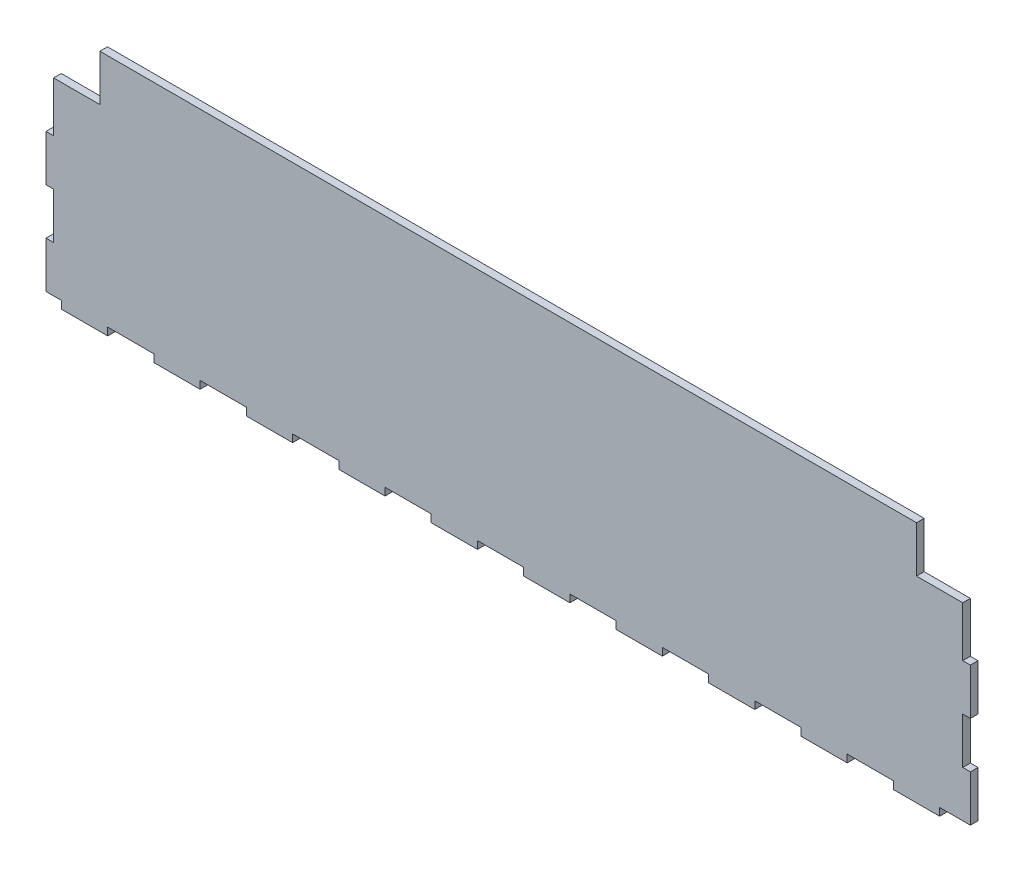
SolidWorks part; units mm, degrees
material "Balsa"
ref_plane "Front Plane" through (0, 0, 0) normal (0, 0, 1) x (1, 0, 0)
ref_plane "Top Plane" through (0, 0, 0) normal (0, 1, 0) x (1, 0, 0)
ref_plane "Right Plane" through (0, 0, 0) normal (1, 0, 0) x (0, 0, -1)
sketch "Sketch1" plane through (0, 0, 0) normal (0, 0, 1) x (1, 0, 0)
  line L0 (393.4, -121.5124) -> (393.4, -39.8043)
  line L1 (393.4, -39.8043) -> (0, -39.8043) construction
  line L2 (0, -39.8043) -> (0, -121.5124)
  line L3 (0, -121.5124) -> (393.4, -121.5124)
  line L4 (0, -138.3774) -> (0, -39.8043) construction
  line L5 (373.4, -39.8043) -> (20, -39.8043) construction
  line L6 (373.4, -39.8043) -> (373.4, -19.8043)
  line L7 (373.4, -19.8043) -> (20, -19.8043)
  line L8 (20, -39.8043) -> (20, -19.8043)
  line L9 (373.4, -39.8043) -> (20, -19.8043) construction
  line L10 (373.4, -19.8043) -> (20, -39.8043) construction
  line L13 (20.7, -19.8043) -> (372.7, -19.8043) construction
  line L14 (393.4, -39.8043) -> (393.4, -138.3812) construction
  line L19 (393.4, -39.8043) -> (373.4, -39.8043)
  line L20 (0, -39.8043) -> (20, -39.8043)
  point P12 (196.7, -29.8043)
  dimension "D1" = 20
  dimension "D2" = 20
  dimension "D3" = 20
extrude "Boss-Extrude1" add sketch "Sketch1" against normal blind 3.3 contours L2 L3 L0 L1 | L8 L1 L6 L7 region at (196.7, -71.4918, 0)
sketch "Sketch2" plane through (0, 0, 0) normal (0, 0, 1) x (1, 0, 0)
  line L0 (343.4, -121.5124) -> (323.4, -121.5124)
  line L1 (383.4, -121.5124) -> (363.4, -121.5124)
  line L2 (383.4, -121.5124) -> (383.4, -124.8124)
  line L3 (383.4, -124.8124) -> (363.4, -124.8124)
  line L4 (363.4, -121.5124) -> (363.4, -124.8124)
  line L5 (383.4, -121.5124) -> (363.4, -124.8124) construction
  line L6 (383.4, -124.8124) -> (363.4, -121.5124) construction
  line L7 (343.4, -121.5124) -> (343.4, -124.8124)
  line L8 (343.4, -124.8124) -> (323.4, -124.8124)
  line L9 (323.4, -121.5124) -> (323.4, -124.8124)
  line L10 (343.4, -121.5124) -> (323.4, -124.8124) construction
  line L11 (343.4, -124.8124) -> (323.4, -121.5124) construction
  line L12 (303.4, -121.5124) -> (283.4, -121.5124)
  line L13 (303.4, -121.5124) -> (303.4, -124.8124)
  line L14 (303.4, -124.8124) -> (283.4, -124.8124)
  line L15 (283.4, -121.5124) -> (283.4, -124.8124)
  line L16 (303.4, -121.5124) -> (283.4, -124.8124) construction
  line L17 (303.4, -124.8124) -> (283.4, -121.5124) construction
  line L18 (263.4, -121.5124) -> (243.4, -121.5124)
  line L19 (263.4, -121.5124) -> (263.4, -124.8124)
  line L20 (263.4, -124.8124) -> (243.4, -124.8124)
  line L21 (243.4, -121.5124) -> (243.4, -124.8124)
  line L22 (263.4, -121.5124) -> (243.4, -124.8124) construction
  line L23 (263.4, -124.8124) -> (243.4, -121.5124) construction
  line L24 (223.4, -121.5124) -> (203.4, -121.5124)
  line L25 (223.4, -121.5124) -> (223.4, -124.8124)
  line L26 (223.4, -124.8124) -> (203.4, -124.8124)
  line L27 (203.4, -121.5124) -> (203.4, -124.8124)
  line L28 (223.4, -121.5124) -> (203.4, -124.8124) construction
  line L29 (223.4, -124.8124) -> (203.4, -121.5124) construction
  line L30 (183.4, -121.5124) -> (163.4, -121.5124)
  line L31 (183.4, -121.5124) -> (183.4, -124.8124)
  line L32 (183.4, -124.8124) -> (163.4, -124.8124)
  line L33 (163.4, -121.5124) -> (163.4, -124.8124)
  line L34 (183.4, -121.5124) -> (163.4, -124.8124) construction
  line L35 (183.4, -124.8124) -> (163.4, -121.5124) construction
  line L36 (143.4, -121.5124) -> (123.4, -121.5124)
  line L37 (143.4, -121.5124) -> (143.4, -124.8124)
  line L38 (143.4, -124.8124) -> (123.4, -124.8124)
  line L39 (123.4, -121.5124) -> (123.4, -124.8124)
  line L40 (143.4, -121.5124) -> (123.4, -124.8124) construction
  line L41 (143.4, -124.8124) -> (123.4, -121.5124) construction
  line L42 (103.4, -121.5124) -> (83.4, -121.5124)
  line L43 (103.4, -121.5124) -> (103.4, -124.8124)
  line L44 (103.4, -124.8124) -> (83.4, -124.8124)
  line L45 (83.4, -121.5124) -> (83.4, -124.8124)
  line L46 (103.4, -121.5124) -> (83.4, -124.8124) construction
  line L47 (103.4, -124.8124) -> (83.4, -121.5124) construction
  line L48 (63.4, -121.5124) -> (43.4, -121.5124)
  line L49 (63.4, -121.5124) -> (63.4, -124.8124)
  line L50 (63.4, -124.8124) -> (43.4, -124.8124)
  line L51 (43.4, -121.5124) -> (43.4, -124.8124)
  line L52 (63.4, -121.5124) -> (43.4, -124.8124) construction
  line L53 (63.4, -124.8124) -> (43.4, -121.5124) construction
  line L54 (23.4, -121.5124) -> (3.4, -121.5124)
  line L55 (23.4, -121.5124) -> (23.4, -124.8124)
  line L56 (23.4, -124.8124) -> (3.4, -124.8124)
  line L57 (3.4, -121.5124) -> (3.4, -124.8124)
  line L58 (23.4, -121.5124) -> (3.4, -124.8124) construction
  line L59 (23.4, -124.8124) -> (3.4, -121.5124) construction
  point P4 (373.4, -123.1624)
  point P13 (333.4, -123.1624)
  point P18 (293.4, -123.1624)
  point P23 (253.4, -123.1624)
  point P28 (213.4, -123.1624)
  point P33 (173.4, -123.1624)
  point P38 (133.4, -123.1624)
  point P43 (93.4, -123.1624)
  point P48 (53.4, -123.1624)
  point P53 (13.4, -123.1624)
  dimension "D1" = 10
extrude "Boss-Extrude2" add sketch "Sketch2" against normal blind 3.3
sketch "Sketch3" plane through (0, 0, 0) normal (0, 0, 1) x (1, 0, 0)
  line L0 (396.7, -39.8043) -> (396.7, -61.5124) construction
  line L1 (393.4, -121.5124) -> (396.7, -121.5124)
  line L2 (393.4, -121.5124) -> (393.4, -101.5124)
  line L3 (393.4, -101.5124) -> (396.7, -101.5124)
  line L4 (396.7, -121.5124) -> (396.7, -101.5124)
  line L5 (393.4, -121.5124) -> (396.7, -101.5124) construction
  line L6 (393.4, -101.5124) -> (396.7, -121.5124) construction
  line L7 (393.4, -81.5124) -> (396.7, -81.5124)
  line L8 (393.4, -81.5124) -> (393.4, -61.5124)
  line L9 (393.4, -61.5124) -> (396.7, -61.5124)
  line L10 (396.7, -81.5124) -> (396.7, -61.5124)
  line L11 (393.4, -81.5124) -> (396.7, -61.5124) construction
  line L12 (393.4, -61.5124) -> (396.7, -81.5124) construction
  line L15 (-3.3, -124.4404) -> (-3.3, -121.5124) construction
  line L16 (0, -121.5124) -> (-3.3, -121.5124)
  line L17 (0, -121.5124) -> (0, -101.5124)
  line L18 (0, -101.5124) -> (-3.3, -101.5124)
  line L19 (-3.3, -121.5124) -> (-3.3, -101.5124)
  line L20 (0, -121.5124) -> (-3.3, -101.5124) construction
  line L21 (0, -101.5124) -> (-3.3, -121.5124) construction
  line L22 (0, -81.5124) -> (-3.3, -81.5124)
  line L23 (0, -81.5124) -> (0, -61.5124)
  line L24 (0, -61.5124) -> (-3.3, -61.5124)
  line L25 (-3.3, -81.5124) -> (-3.3, -61.5124)
  line L26 (0, -81.5124) -> (-3.3, -61.5124) construction
  line L27 (0, -61.5124) -> (-3.3, -81.5124) construction
  point P4 (395.05, -111.5124)
  point P14 (395.05, -71.5124)
  point P21 (-1.65, -111.5124)
  point P27 (-1.65, -71.5124)
  dimension "D1" = 20
  dimension "D3" = 20
  dimension "D2" = 2
  dimension "D4" = 2
extrude "Boss-Extrude3" add sketch "Sketch3" against normal blind 3.3
